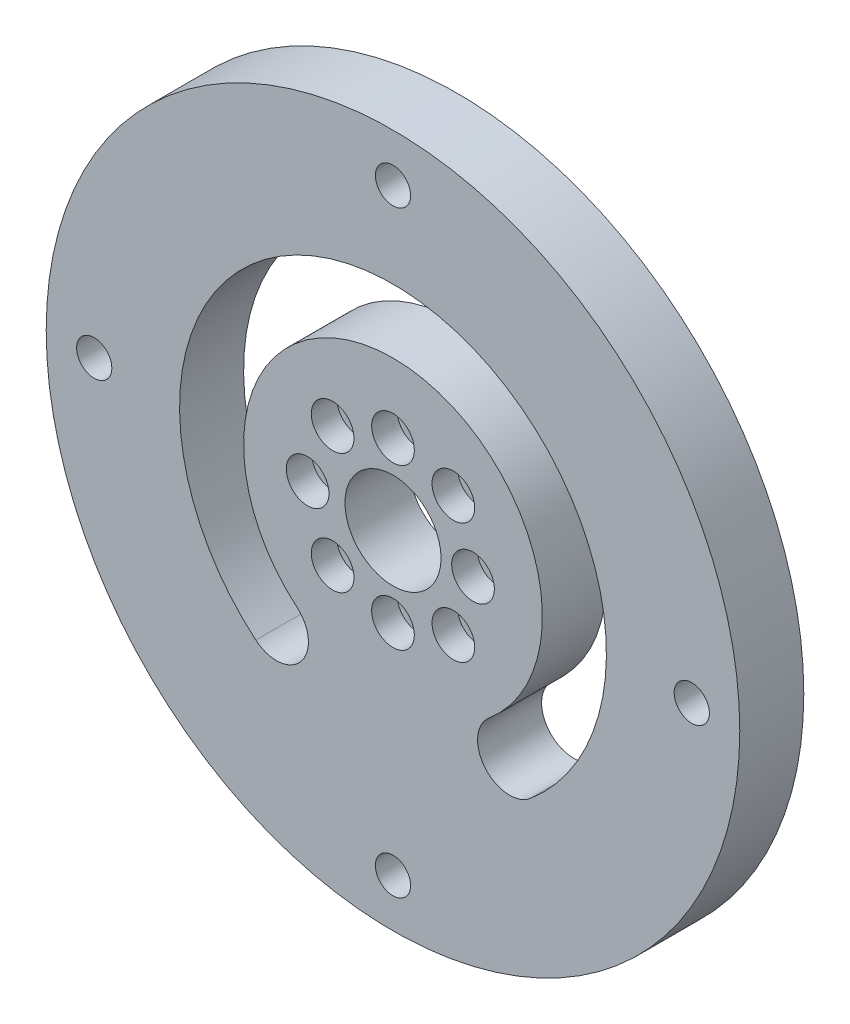
SolidWorks part; units mm, degrees
ref_plane "Front Plane" through (0, 0, 0) normal (0, 0, 1) x (1, 0, 0)
ref_plane "Top Plane" through (0, 0, 0) normal (0, 1, 0) x (1, 0, 0)
ref_plane "Right Plane" through (0, 0, 0) normal (1, 0, 0) x (0, 0, -1)
sketch "Sketch1" plane through (0, 0, 0) normal (0, 0, 1) x (1, 0, 0)
  circle A0 centre (0, 0) radius 32.5
  dimension "D1" = 65
extrude "Boss-Extrude1" add sketch "Sketch1" along normal blind 6
sketch "Sketch16" plane through (0, 0, 6) normal (0, 0, 1) x (1, 0, 0)
  line L0 (-8, 0) -> (0, 0) construction
  circle A1 centre (-8, 0) radius 1
  circle A4 centre (-5.6569, 5.6569) radius 1
  circle A5 centre (0, 8) radius 1
  circle A6 centre (5.6569, 5.6569) radius 1
  circle A7 centre (8, 0) radius 1
  circle A8 centre (5.6569, -5.6569) radius 1
  circle A9 centre (0, -8) radius 1
  circle A10 centre (-5.6569, -5.6569) radius 1
  point P22 (0, 0)
  dimension "D1" = 8
  dimension "D2" = 2
  dimension "D3" = 8
extrude "Cut-Extrude8" cut sketch "Sketch16" against normal through all
sketch "Sketch17" plane through (0, 0, 6) normal (0, 0, 1) x (1, 0, 0)
  circle A0 centre (7.5, 0) radius 2
  circle A1 centre (-8, 0) radius 2
  circle A2 centre (0, -7.5) radius 2
  circle A3 centre (0, 7.5) radius 2
  circle A4 centre (-5.6569, 5.6569) radius 2
  circle A5 centre (5.6569, 5.6569) radius 2
  circle A6 centre (5.6569, -5.6569) radius 2
  circle A7 centre (-5.6569, -5.6569) radius 2
  dimension "D1" = 4
extrude "Cut-Extrude9" cut sketch "Sketch17" against normal blind 2.4
sketch "Sketch18" plane through (0, 0, 0) normal (0, 0, -1) x (-1, 0, 0)
  circle A0 centre (0, 0) radius 4.5
  dimension "D1" = 9
extrude "Cut-Extrude10" cut sketch "Sketch18" against normal through all
sketch "Sketch19" plane through (0, 0, 6) normal (0, 0, 1) x (1, 0, 0)
  line L0 (0, 28) -> (0, 0) construction
  circle A0 centre (0, 28) radius 1.65
  circle A1 centre (28, 0) radius 1.65
  circle A2 centre (0, -28) radius 1.65
  circle A3 centre (-28, 0) radius 1.65
  point P0 (0, 0)
  point P13 (0, 0)
  dimension "D2" = 3.3
  dimension "D1" = 28
  dimension "D3" = 4
extrude "Cut-Extrude11" cut sketch "Sketch19" against normal blind 10
sketch "Sketch20" plane through (0, 0, 0) normal (0, 0, -1) x (-1, 0, 0)
  line L1 (1.6166, 30.8) -> (-1.6166, 30.8)
  line L2 (-1.6166, 30.8) -> (-3.2332, 28)
  line L3 (-3.2332, 28) -> (-1.6166, 25.2)
  line L4 (-1.6166, 25.2) -> (1.6166, 25.2)
  line L5 (1.6166, 25.2) -> (3.2332, 28)
  line L6 (3.2332, 28) -> (1.6166, 30.8)
  line L7 (29.6166, 2.8) -> (26.3834, 2.8)
  line L8 (26.3834, 2.8) -> (24.7668, 0)
  line L9 (24.7668, 0) -> (26.3834, -2.8)
  line L10 (26.3834, -2.8) -> (29.6166, -2.8)
  line L11 (29.6166, -2.8) -> (31.2332, 0)
  line L12 (31.2332, 0) -> (29.6166, 2.8)
  line L13 (1.6166, -25.2) -> (-1.6166, -25.2)
  line L14 (-1.6166, -25.2) -> (-3.2332, -28)
  line L15 (-3.2332, -28) -> (-1.6166, -30.8)
  line L16 (-1.6166, -30.8) -> (1.6166, -30.8)
  line L17 (1.6166, -30.8) -> (3.2332, -28)
  line L18 (3.2332, -28) -> (1.6166, -25.2)
  line L19 (-26.3834, 2.8) -> (-29.6166, 2.8)
  line L20 (-29.6166, 2.8) -> (-31.2332, 0)
  line L21 (-31.2332, 0) -> (-29.6166, -2.8)
  line L22 (-29.6166, -2.8) -> (-26.3834, -2.8)
  line L23 (-26.3834, -2.8) -> (-24.7668, 0)
  line L24 (-24.7668, 0) -> (-26.3834, 2.8)
  circle A0 centre (0, 28) radius 2.8 construction
  circle A1 centre (28, 0) radius 2.8 construction
  circle A2 centre (0, -28) radius 2.8 construction
  circle A3 centre (-28, 0) radius 2.8 construction
  point P28 (0, 30.8)
  dimension "D1" = 5.6
extrude "Cut-Extrude12" cut sketch "Sketch20" against normal blind 3
sketch "Sketch21" plane through (0, 0, 6) normal (0, 0, 1) x (1, 0, 0)
  line L0 (0, 0) -> (0, -18.8551) construction
  line L1 (0, 0) -> (12.8558, -15.3209) construction
  line L2 (0, 0) -> (-12.8558, -15.3209) construction
  arc A0 (12.8558, -15.3209) -> (-12.8558, -15.3209) centre (0, 0) ccw
  arc A1 (8.999, -10.7246) -> (-8.999, -10.7246) centre (0, 0) ccw
  arc A2 (-12.8558, -15.3209) -> (-8.999, -10.7246) centre (-10.9274, -13.0228) ccw
  arc A3 (8.999, -10.7246) -> (12.8558, -15.3209) centre (10.9274, -13.0228) ccw
  point P8 (0, 0)
  dimension "D3" = 14
  dimension "D1" = 6
  dimension "D2" = 40
extrude "Cut-Extrude13" cut sketch "Sketch21" against normal through all
